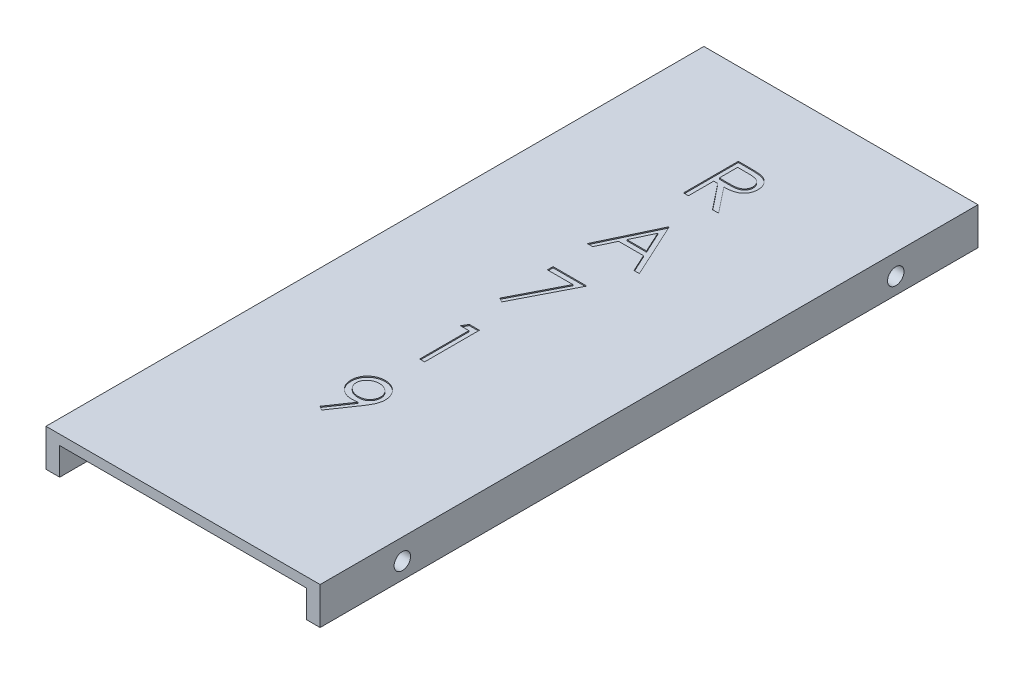
SolidWorks part; units mm, degrees
material "Cedar"
ref_plane "Front Plane" through (0, 0, 0) normal (0, 0, 1) x (1, 0, 0)
ref_plane "Top Plane" through (0, 0, 0) normal (0, 1, 0) x (1, 0, 0)
ref_plane "Right Plane" through (0, 0, 0) normal (1, 0, 0) x (0, 0, -1)
sketch "Sketch2" plane through (0, 0, 0) normal (0, 0, 1) x (1, 0, 0)
  line L0 (0, 0) -> (0, 68)
  line L1 (0, 68) -> (500, 68)
  line L2 (0, 0) -> (25, 0)
  line L3 (25, 50) -> (475, 50)
  line L4 (25, 50) -> (25, 0)
  line L5 (500, 68) -> (500, 0)
  line L6 (500, 0) -> (475, 0)
  line L7 (475, 0) -> (475, 50)
  dimension "D1" = 68
  dimension "D2" = 500
  dimension "D3" = 25
  dimension "D4" = 50
  dimension "D5" = 68
  dimension "D6" = 25
  dimension "D7" = 50
extrude "Boss-Extrude1" add sketch "Sketch2" along normal blind 1200
sketch "Sketch3" plane through (500, 0, 0) normal (1, 0, 0) x (0, 0, -1)
  line L1 (-1200, 0) -> (0, 0) construction
  line L2 (-1200, 0) -> (-1200, 68) construction
  line L3 (0, 0) -> (0, 68) construction
  circle A0 centre (-1050, 30) radius 15
  circle A1 centre (-150, 30) radius 15
  dimension "D1" = 30
  dimension "D3" = 30
  dimension "D4" = 30
  dimension "D2" = 150
  dimension "D5" = 150
  dimension "D6" = 30
extrude "Cut-Extrude1" cut sketch "Sketch3" against normal through all
sketch "Sketch4" plane through (0, 68, 0) normal (0, 1, 0) x (1, 0, 0)
  line L0 (0, -1200) -> (0, 0) construction
  line L1 (500, 0) -> (0, 0) construction
  text T0 "R\r\nA\r\n7\r\n1\r\n9" font "Century Gothic" height 100
  dimension "D1" = 200
  dimension "D2" = 250
extrude "Cut-Extrude2" cut sketch "Sketch4" against normal blind 2
sketch "Sketch5" plane through (0, 50, 0) normal (0, -1, 0) x (1, 0, 0)
  line L0 (0, 1200) -> (0, 0) construction
  line L1 (25, 1200) -> (475, 1200) construction
  text T0 "R\r\nA\r\n7\r\n1\r\n9" font "Century Gothic" height 100
  dimension "D1" = 200
  dimension "D2" = 250
extrude "Cut-Extrude3" cut sketch "Sketch5" against normal blind 2
